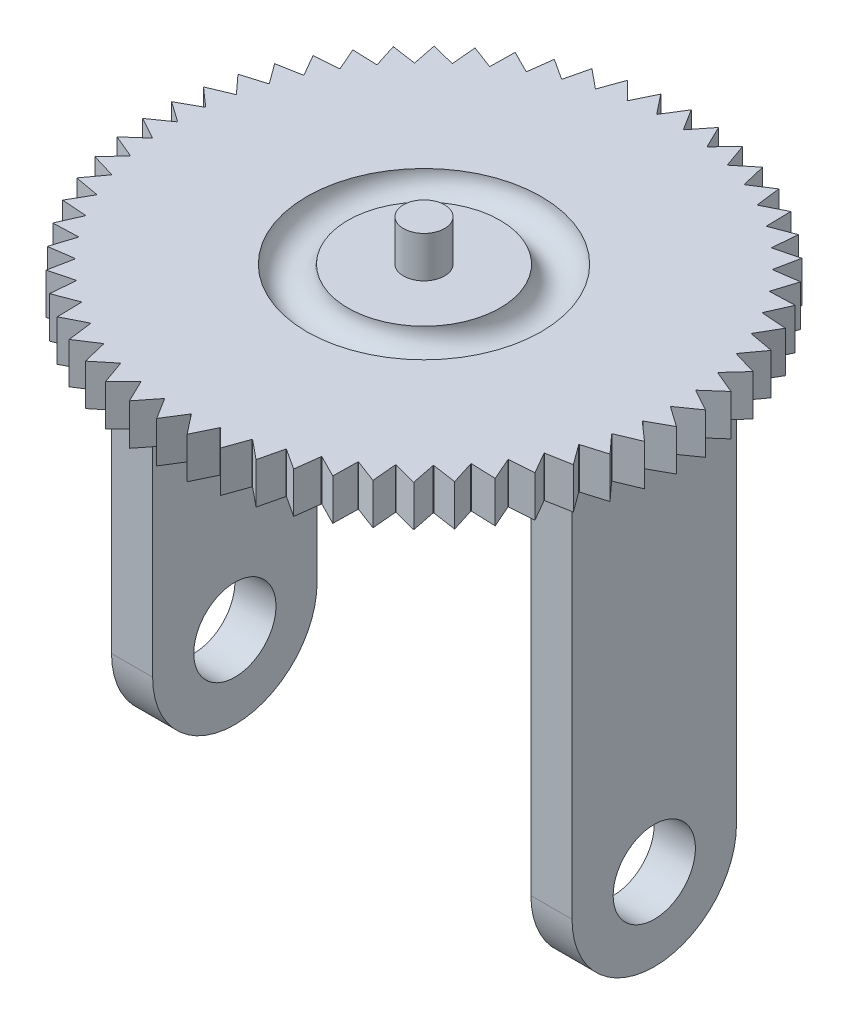
SolidWorks part; units mm, degrees
material "1023 Carbon Steel Sheet (SS)"
ref_plane "Front Plane" through (0, 0, 0) normal (0, 0, 1) x (1, 0, 0)
ref_plane "Top Plane" through (0, 0, 0) normal (0, 1, 0) x (1, 0, 0)
ref_plane "Right Plane" through (0, 0, 0) normal (1, 0, 0) x (0, 0, -1)
sketch "Sketch1" plane through (0, 0, 0) normal (0, 1, 0) x (1, 0, 0)
  circle A0 centre (0, 0) radius 76.2
  dimension "D1" = 152.4
extrude "Boss-Extrude1" add sketch "Sketch1" along normal blind 12.7 contours A0
sketch "Sketch2" plane through (0, 12.7, 0) normal (0, 1, 0) x (1, 0, 0)
  circle A0 centre (0, 0) radius 6.35
  dimension "D1" = 12.7
extrude "Boss-Extrude2" add sketch "Sketch2" along normal blind 12.7
sketch "Sketch4" plane through (0, 0, 0) normal (0, 0, 1) x (1, 0, 0)
  line L0 (76.2, 12.7) -> (-76.2, 12.7) construction
  line L1 (0, 0) -> (0, 24.8401)
  line L2 (-36.195, 12.7) -> (-23.495, 12.7)
  arc A0 (-36.195, 12.7) -> (-23.495, 12.7) centre (-29.845, 12.7) ccw
  dimension "D1" = 6.35
  dimension "D2" = 23.495
revolve "Cut-Revolve3" cut sketch "Sketch4" angle 360 about L1 region at (-29.845, 10.005, 0)
sketch "Sketch5" plane through (0, 0, 0) normal (0, -1, 0) x (1, 0, 0)
  line L0 (0, -13.97) -> (0, 13.97) construction
  line L1 (58.42, -25.4) -> (71.12, -25.4)
  line L2 (58.42, -25.4) -> (58.42, 25.4)
  line L3 (58.42, 25.4) -> (71.12, 25.4)
  line L4 (71.12, -25.4) -> (71.12, 25.4)
  line L5 (58.42, -25.4) -> (71.12, 25.4) construction
  line L6 (58.42, 25.4) -> (71.12, -25.4) construction
  line L7 (-58.42, 25.4) -> (-71.12, 25.4)
  line L8 (-71.12, -25.4) -> (-71.12, 25.4)
  line L9 (-58.42, -25.4) -> (-71.12, -25.4)
  line L10 (-58.42, -25.4) -> (-58.42, 25.4)
  point P0 (64.77, 0)
  dimension "D1" = 50.8
  dimension "D2" = 12.7
  dimension "D3" = 64.77
extrude "Boss-Extrude3" add sketch "Sketch5" along normal blind 139.7
sketch "Sketch6" plane through (-71.12, 0, 0) normal (-1, 0, 0) x (0, 0, 1)
  line L0 (-25.4, -114.3) -> (-25.4, -139.7)
  line L1 (-25.4, -139.7) -> (-25.4, 0) construction
  line L2 (-25.4, -139.7) -> (25.4, -139.7)
  line L3 (25.4, -139.7) -> (25.4, -114.3)
  line L4 (25.4, -139.7) -> (25.4, 0) construction
  circle A0 centre (0, -114.3) radius 12.7
  arc A1 (-25.4, -114.3) -> (25.4, -114.3) centre (0, -114.3) ccw
  point P14 (0, -139.7)
  line M4 (-25.4, 0) -> (-25.4, -139.7)
  line M5 (-25.4, -139.7) -> (25.4, -139.7)
  line M6 (25.4, -139.7) -> (25.4, 0)
  dimension "D2" = 25.4
  dimension "D1" = 114.3
extrude "Cut-Extrude1" cut sketch "Sketch6" against normal through all contours A1 M4 M5 | A1 L2 M6 | A0 region at (-71.12, -134.0265, -19.7265) region at (-71.12, -134.0265, 19.7265) region at (-71.12, -114.3, 0)
sketch "Sketch7" plane through (0, 12.7, 0) normal (0, 1, 0) x (1, 0, 0)
  line L0 (0, 76.2) -> (0, 82.55) construction
  line L1 (0, 82.55) -> (-4.0454, 76.0925)
  line L2 (0, 82.55) -> (4.0454, 76.0925)
  line L3 (-4.0454, 76.0925) -> (4.0454, 76.0925)
  line L4 (4.2053, 76.0839) -> (12.2488, 75.2091)
  line L5 (8.9252, 82.0661) -> (12.2488, 75.2091)
  line L6 (8.9252, 82.0661) -> (4.2053, 76.0839)
  line L7 (12.4068, 75.1832) -> (20.3085, 73.4439)
  line L8 (17.7458, 80.62) -> (20.3085, 73.4439)
  line L9 (17.7458, 80.62) -> (12.4068, 75.1832)
  line L10 (20.4628, 73.4011) -> (28.1301, 70.8176)
  line L11 (26.3583, 78.2288) -> (28.1301, 70.8176)
  line L12 (26.3583, 78.2288) -> (20.4628, 73.4011)
  line L13 (28.2789, 70.7584) -> (35.622, 67.3611)
  line L14 (34.6618, 74.9204) -> (35.622, 67.3611)
  line L15 (34.6618, 74.9204) -> (28.2789, 70.7584)
  line L16 (35.7634, 67.2861) -> (42.6962, 63.1148)
  line L17 (42.559, 70.7336) -> (42.6962, 63.1148)
  line L18 (42.559, 70.7336) -> (35.7634, 67.2861)
  line L19 (42.8287, 63.0249) -> (49.2698, 58.1285)
  line L20 (49.9571, 65.7175) -> (49.2698, 58.1285)
  line L21 (49.9571, 65.7175) -> (42.8287, 63.0249)
  line L22 (49.3918, 58.0249) -> (55.2658, 52.4608)
  line L23 (56.7696, 59.9309) -> (55.2658, 52.4608)
  line L24 (56.7696, 59.9309) -> (49.3918, 58.0249)
  line L25 (55.3759, 52.3445) -> (60.6138, 46.178)
  line L26 (62.9165, 53.4417) -> (60.6138, 46.178)
  line L27 (62.9165, 53.4417) -> (55.3759, 52.3445)
  line L28 (60.7107, 46.0505) -> (65.2512, 39.3538)
  line L29 (68.3257, 46.326) -> (65.2512, 39.3538)
  line L30 (68.3257, 46.326) -> (60.7107, 46.0505)
  line L31 (65.3338, 39.2166) -> (69.1236, 32.0682)
  line L32 (72.9339, 38.6671) -> (69.1236, 32.0682)
  line L33 (72.9339, 38.6671) -> (65.3338, 39.2166)
  line L34 (69.1908, 31.9229) -> (72.1856, 24.4066)
  line L35 (76.687, 30.5549) -> (72.1856, 24.4066)
  line L36 (76.687, 30.5549) -> (69.1908, 31.9229)
  line L37 (72.2367, 24.2549) -> (74.4012, 16.4589)
  line L38 (79.5411, 22.0845) -> (74.4012, 16.4589)
  line L39 (79.5411, 22.0845) -> (72.2367, 24.2549)
  line L40 (74.4357, 16.3026) -> (75.7446, 8.3183)
  line L41 (81.4625, 13.3551) -> (75.7446, 8.3183)
  line L42 (81.4625, 13.3551) -> (74.4357, 16.3026)
  line L43 (75.7619, 8.1591) -> (76.2, 0.0801)
  line L44 (82.4289, 4.4692) -> (76.2, 0.0801)
  line L45 (82.4289, 4.4692) -> (75.7619, 8.1591)
  line L46 (76.2, -0.0801) -> (75.7619, -8.1591)
  line L47 (82.4289, -4.4692) -> (75.7619, -8.1591)
  line L48 (82.4289, -4.4692) -> (76.2, -0.0801)
  line L49 (75.7446, -8.3183) -> (74.4357, -16.3026)
  line L50 (81.4625, -13.3551) -> (74.4357, -16.3026)
  line L51 (81.4625, -13.3551) -> (75.7446, -8.3183)
  line L52 (74.4012, -16.4589) -> (72.2367, -24.2549)
  line L53 (79.5411, -22.0845) -> (72.2367, -24.2549)
  line L54 (79.5411, -22.0845) -> (74.4012, -16.4589)
  line L55 (72.1856, -24.4066) -> (69.1908, -31.9229)
  line L56 (76.687, -30.5549) -> (69.1908, -31.9229)
  line L57 (76.687, -30.5549) -> (72.1856, -24.4066)
  line L58 (69.1236, -32.0682) -> (65.3338, -39.2166)
  line L59 (72.9339, -38.6671) -> (65.3338, -39.2166)
  line L60 (72.9339, -38.6671) -> (69.1236, -32.0682)
  line L61 (65.2512, -39.3538) -> (60.7107, -46.0505)
  line L62 (68.3257, -46.326) -> (60.7107, -46.0505)
  line L63 (68.3257, -46.326) -> (65.2512, -39.3538)
  line L64 (60.6138, -46.178) -> (55.3759, -52.3445)
  line L65 (62.9165, -53.4417) -> (55.3759, -52.3445)
  line L66 (62.9165, -53.4417) -> (60.6138, -46.178)
  line L67 (55.2658, -52.4608) -> (49.3918, -58.0249)
  line L68 (56.7696, -59.9309) -> (49.3918, -58.0249)
  line L69 (56.7696, -59.9309) -> (55.2658, -52.4608)
  line L70 (49.2698, -58.1285) -> (42.8287, -63.0249)
  line L71 (49.9571, -65.7175) -> (42.8287, -63.0249)
  line L72 (49.9571, -65.7175) -> (49.2698, -58.1285)
  line L73 (42.6962, -63.1148) -> (35.7634, -67.2861)
  line L74 (42.559, -70.7336) -> (35.7634, -67.2861)
  line L75 (42.559, -70.7336) -> (42.6962, -63.1148)
  line L76 (35.622, -67.3611) -> (28.2789, -70.7584)
  line L77 (34.6618, -74.9204) -> (28.2789, -70.7584)
  line L78 (34.6618, -74.9204) -> (35.622, -67.3611)
  line L79 (28.1301, -70.8176) -> (20.4628, -73.4011)
  line L80 (26.3583, -78.2288) -> (20.4628, -73.4011)
  line L81 (26.3583, -78.2288) -> (28.1301, -70.8176)
  line L82 (20.3085, -73.4439) -> (12.4068, -75.1832)
  line L83 (17.7458, -80.62) -> (12.4068, -75.1832)
  line L84 (17.7458, -80.62) -> (20.3085, -73.4439)
  line L85 (12.2488, -75.2091) -> (4.2053, -76.0839)
  line L86 (8.9252, -82.0661) -> (4.2053, -76.0839)
  line L87 (8.9252, -82.0661) -> (12.2488, -75.2091)
  line L88 (4.0454, -76.0925) -> (-4.0454, -76.0925)
  line L89 (0, -82.55) -> (-4.0454, -76.0925)
  line L90 (0, -82.55) -> (4.0454, -76.0925)
  line L91 (-4.2053, -76.0839) -> (-12.2488, -75.2091)
  line L92 (-8.9252, -82.0661) -> (-12.2488, -75.2091)
  line L93 (-8.9252, -82.0661) -> (-4.2053, -76.0839)
  line L94 (-12.4068, -75.1832) -> (-20.3085, -73.4439)
  line L95 (-17.7458, -80.62) -> (-20.3085, -73.4439)
  line L96 (-17.7458, -80.62) -> (-12.4068, -75.1832)
  line L97 (-20.4628, -73.4011) -> (-28.1301, -70.8176)
  line L98 (-26.3583, -78.2288) -> (-28.1301, -70.8176)
  line L99 (-26.3583, -78.2288) -> (-20.4628, -73.4011)
  line L100 (-28.2789, -70.7584) -> (-35.622, -67.3611)
  line L101 (-34.6618, -74.9204) -> (-35.622, -67.3611)
  line L102 (-34.6618, -74.9204) -> (-28.2789, -70.7584)
  line L103 (-35.7634, -67.2861) -> (-42.6962, -63.1148)
  line L104 (-42.559, -70.7336) -> (-42.6962, -63.1148)
  line L105 (-42.559, -70.7336) -> (-35.7634, -67.2861)
  line L106 (-42.8287, -63.0249) -> (-49.2698, -58.1285)
  line L107 (-49.9571, -65.7175) -> (-49.2698, -58.1285)
  line L108 (-49.9571, -65.7175) -> (-42.8287, -63.0249)
  line L109 (-49.3918, -58.0249) -> (-55.2658, -52.4608)
  line L110 (-56.7696, -59.9309) -> (-55.2658, -52.4608)
  line L111 (-56.7696, -59.9309) -> (-49.3918, -58.0249)
  line L112 (-55.3759, -52.3445) -> (-60.6138, -46.178)
  line L113 (-62.9165, -53.4417) -> (-60.6138, -46.178)
  line L114 (-62.9165, -53.4417) -> (-55.3759, -52.3445)
  line L115 (-60.7107, -46.0505) -> (-65.2512, -39.3538)
  line L116 (-68.3257, -46.326) -> (-65.2512, -39.3538)
  line L117 (-68.3257, -46.326) -> (-60.7107, -46.0505)
  line L118 (-65.3338, -39.2166) -> (-69.1236, -32.0682)
  line L119 (-72.9339, -38.6671) -> (-69.1236, -32.0682)
  line L120 (-72.9339, -38.6671) -> (-65.3338, -39.2166)
  line L121 (-69.1908, -31.9229) -> (-72.1856, -24.4066)
  line L122 (-76.687, -30.5549) -> (-72.1856, -24.4066)
  line L123 (-76.687, -30.5549) -> (-69.1908, -31.9229)
  line L124 (-72.2367, -24.2549) -> (-74.4012, -16.4589)
  line L125 (-79.5411, -22.0845) -> (-74.4012, -16.4589)
  line L126 (-79.5411, -22.0845) -> (-72.2367, -24.2549)
  line L127 (-74.4357, -16.3026) -> (-75.7446, -8.3183)
  line L128 (-81.4625, -13.3551) -> (-75.7446, -8.3183)
  line L129 (-81.4625, -13.3551) -> (-74.4357, -16.3026)
  line L130 (-75.7619, -8.1591) -> (-76.2, -0.0801)
  line L131 (-82.4289, -4.4692) -> (-76.2, -0.0801)
  line L132 (-82.4289, -4.4692) -> (-75.7619, -8.1591)
  line L133 (-76.2, 0.0801) -> (-75.7619, 8.1591)
  line L134 (-82.4289, 4.4692) -> (-75.7619, 8.1591)
  line L135 (-82.4289, 4.4692) -> (-76.2, 0.0801)
  line L136 (-75.7446, 8.3183) -> (-74.4357, 16.3026)
  line L137 (-81.4625, 13.3551) -> (-74.4357, 16.3026)
  line L138 (-81.4625, 13.3551) -> (-75.7446, 8.3183)
  line L139 (-74.4012, 16.4589) -> (-72.2367, 24.2549)
  line L140 (-79.5411, 22.0845) -> (-72.2367, 24.2549)
  line L141 (-79.5411, 22.0845) -> (-74.4012, 16.4589)
  line L142 (-72.1856, 24.4066) -> (-69.1908, 31.9229)
  line L143 (-76.687, 30.5549) -> (-69.1908, 31.9229)
  line L144 (-76.687, 30.5549) -> (-72.1856, 24.4066)
  line L145 (-69.1236, 32.0682) -> (-65.3338, 39.2166)
  line L146 (-72.9339, 38.6671) -> (-65.3338, 39.2166)
  line L147 (-72.9339, 38.6671) -> (-69.1236, 32.0682)
  line L148 (-65.2512, 39.3538) -> (-60.7107, 46.0505)
  line L149 (-68.3257, 46.326) -> (-60.7107, 46.0505)
  line L150 (-68.3257, 46.326) -> (-65.2512, 39.3538)
  line L151 (-60.6138, 46.178) -> (-55.3759, 52.3445)
  line L152 (-62.9165, 53.4417) -> (-55.3759, 52.3445)
  line L153 (-62.9165, 53.4417) -> (-60.6138, 46.178)
  line L154 (-55.2658, 52.4608) -> (-49.3918, 58.0249)
  line L155 (-56.7696, 59.9309) -> (-49.3918, 58.0249)
  line L156 (-56.7696, 59.9309) -> (-55.2658, 52.4608)
  line L157 (-49.2698, 58.1285) -> (-42.8287, 63.0249)
  line L158 (-49.9571, 65.7175) -> (-42.8287, 63.0249)
  line L159 (-49.9571, 65.7175) -> (-49.2698, 58.1285)
  line L160 (-42.6962, 63.1148) -> (-35.7634, 67.2861)
  line L161 (-42.559, 70.7336) -> (-35.7634, 67.2861)
  line L162 (-42.559, 70.7336) -> (-42.6962, 63.1148)
  line L163 (-35.622, 67.3611) -> (-28.2789, 70.7584)
  line L164 (-34.6618, 74.9204) -> (-28.2789, 70.7584)
  line L165 (-34.6618, 74.9204) -> (-35.622, 67.3611)
  line L166 (-28.1301, 70.8176) -> (-20.4628, 73.4011)
  line L167 (-26.3583, 78.2288) -> (-20.4628, 73.4011)
  line L168 (-26.3583, 78.2288) -> (-28.1301, 70.8176)
  line L169 (-20.3085, 73.4439) -> (-12.4068, 75.1832)
  line L170 (-17.7458, 80.62) -> (-12.4068, 75.1832)
  line L171 (-17.7458, 80.62) -> (-20.3085, 73.4439)
  line L172 (-12.2488, 75.2091) -> (-4.2053, 76.0839)
  line L173 (-8.9252, 82.0661) -> (-4.2053, 76.0839)
  line L174 (-8.9252, 82.0661) -> (-12.2488, 75.2091)
  circle A0 centre (0, 0) radius 76.2 construction
  point P182 (0, 0)
  dimension "D1" = 6.35
  dimension "D2" = 7.62
  dimension "D3" = 58
extrude "Boss-Extrude4" add sketch "Sketch7" against normal blind 12.7
